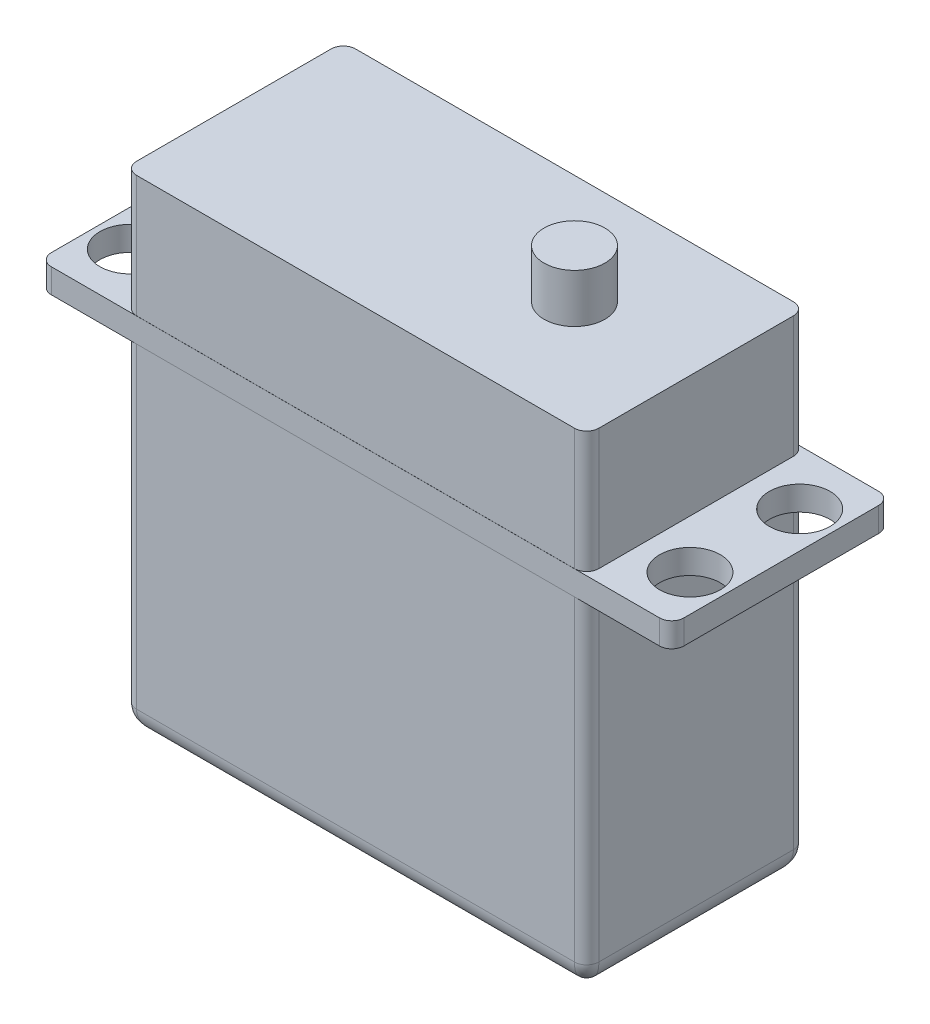
SolidWorks part; units mm, degrees
ref_plane "Front Plane" through (0, 0, 0) normal (0, 0, 1) x (1, 0, 0)
ref_plane "Top Plane" through (0, 0, 0) normal (0, 1, 0) x (1, 0, 0)
ref_plane "Right Plane" through (0, 0, 0) normal (1, 0, 0) x (0, 0, -1)
sketch "Sketch1" plane through (0, 0, 0) normal (0, 1, 0) x (1, 0, 0)
  line L1 (-19, 9) -> (19, 9)
  line L2 (-19, 9) -> (-19, -9)
  line L3 (-19, -9) -> (19, -9)
  line L4 (19, 9) -> (19, -9)
  line L5 (-19, 9) -> (19, -9) construction
  line L6 (-19, -9) -> (19, 9) construction
  point P0 (0, 0)
  dimension "D1" = 38
  dimension "D2" = 18
extrude "Boss-Extrude1" add sketch "Sketch1" along normal blind 40
ref_plane "Plane1" through (0, 30, 0) normal (0, 1, 0) x (1, 0, 0)
sketch "Sketch2" plane through (0, 30, 0) normal (0, 1, 0) x (1, 0, 0)
  line L0 (19, -9) -> (19, 9) construction
  line L1 (-26, 9.0082) -> (26, 9.0082)
  line L2 (-26, 9.0082) -> (-26, -9.0082)
  line L3 (-26, -9.0082) -> (26, -9.0082)
  line L4 (26, 9.0082) -> (26, -9.0082)
  line L5 (-26, 9.0082) -> (26, -9.0082) construction
  line L6 (-26, -9.0082) -> (26, 9.0082) construction
  point P0 (0, 0)
  dimension "D1" = 7
extrude "Boss-Extrude2" add sketch "Sketch2" against normal blind 2 separate body
sketch "Sketch4" plane through (0, 30, 0) normal (0, 1, 0) x (1, 0, 0)
  line L0 (26, 9.0082) -> (-26, 9.0082) construction
  line L1 (19, -9) -> (19, 9) construction
  line L2 (-26, -9.0082) -> (26, -9.0082) construction
  line L3 (-19, 9) -> (-19, -9) construction
  circle A0 centre (23, 4.5082) radius 2.5
  circle A1 centre (23, -4.5082) radius 2.5
  circle A2 centre (-23, 4.5082) radius 2.5
  circle A3 centre (-23, -4.5082) radius 2.5
  dimension "D1" = 5
  dimension "D4" = 5
  dimension "D5" = 4.5
  dimension "D6" = 4
  dimension "D7" = 2
  dimension "D8" = 4
  dimension "D2" = 4.5
  dimension "D3" = 4
extrude "Cut-Extrude4" cut sketch "Sketch4" against normal blind 2
ref_plane "Plane2" through (0, 40, 0) normal (0, 1, 0) x (1, 0, 0)
sketch "Sketch5" plane through (0, 40, 0) normal (0, 1, 0) x (1, 0, 0)
  line L0 (19, -9) -> (19, 9) construction
  circle A0 centre (9, 0) radius 2.5
  dimension "D1" = 5
  dimension "D2" = 10
extrude "Boss-Extrude3" add sketch "Sketch5" along normal blind 4
fillet "Fillet1" radius 1 1 edges at (19, 20, 9)
fillet "Fillet2" radius 1 2 edges at (-19, 20, 9) (19, 20, -9)
fillet "Fillet3" radius 1 1 edges at (-19, 20, -9)
fillet "Fillet4" radius 2 8 edges at (-18.7071, 0, 8.7071) (-19, 0, 0) (-18.7071, 0, -8.7071) (0, 0, -9) (18.7071, 0, -8.7071) (19, 0, 0) (18.7071, 0, 8.7071) (0, 0, 9)
fillet "Fillet5" radius 1 3 edges at (-26, 29, -9.0082) (26, 29, 9.0082) (26, 29, -9.0082)
fillet "Fillet6" radius 1 1 edges at (-26, 29, 9.0082)
